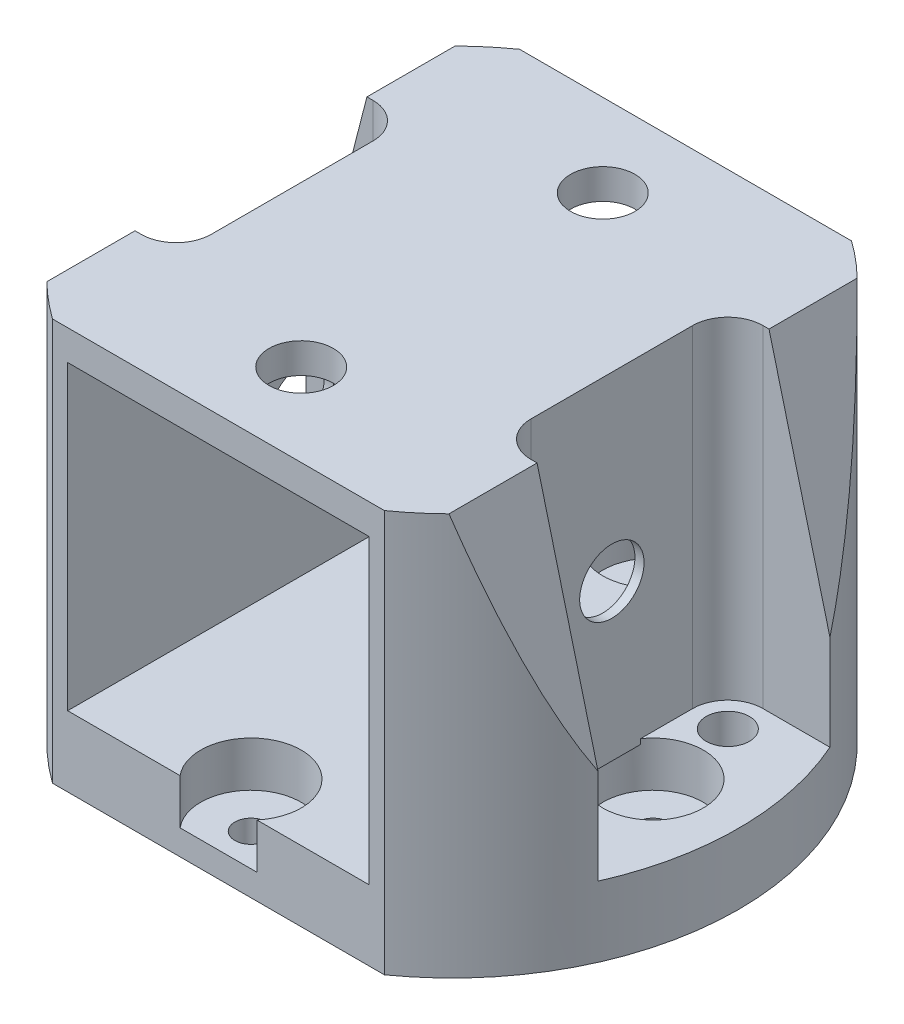
SolidWorks part; units mm, degrees
ref_plane "Front Plane" through (0, 0, 0) normal (0, 0, 1) x (1, 0, 0)
ref_plane "Top Plane" through (0, 0, 0) normal (0, 1, 0) x (1, 0, 0)
ref_plane "Right Plane" through (0, 0, 0) normal (1, 0, 0) x (0, 0, -1)
sketch "Sketch1" plane through (0, 0, 0) normal (0, 0, 1) x (1, 0, 0)
  line L0 (-28.5, 0) -> (-20, 33)
  line L1 (15, 0) -> (-15, 0)
  line L2 (15, 0) -> (15, 30)
  line L3 (15, 30) -> (-15, 30)
  line L4 (-15, 0) -> (-15, 30)
  line L5 (-20, 33) -> (20, 33)
  line L6 (20, 33) -> (28.5, 0)
  line L7 (28.5, 0) -> (28.5, -7)
  line L8 (28.5, -7) -> (-28.5, -7)
  line L9 (-28.5, -7) -> (-28.5, 0)
  line L10 (0, 0) -> (0, -7) construction
  point P15 (0, 33)
  point P16 (0, 30)
  dimension "D1" = 7
  dimension "D2" = 57
  dimension "D3" = 30
  dimension "D4" = 5
  dimension "D5" = 3
extrude "Boss-Extrude1" add sketch "Sketch1" along normal mid plane 57
sketch "Sketch3" plane through (0, 0, 0) normal (0, 1, 0) x (1, 0, 0)
  line L1 (-19.4015, 8.0364) -> (0, 0) construction
  line L2 (0, 0) -> (-20, 0) construction
  line L3 (20, -28.5) -> (-20, -28.5) construction
  line L4 (-15, 28.5) -> (15, 28.5) construction
  line L5 (-15, 28.5) -> (-15, -28.5) construction
  line L6 (-15, -28.5) -> (15, -28.5) construction
  line L7 (15, 28.5) -> (15, -28.5) construction
  line L8 (-15, 28.5) -> (15, -28.5) construction
  line L9 (-15, -28.5) -> (15, 28.5) construction
  circle A1 centre (-19.4015, 8.0364) radius 2.15
  circle A2 centre (-20, 0) radius 1.6
  circle A6 centre (-14.1421, 14.1421) radius 1.6
  circle A7 centre (-8.0364, 19.4015) radius 2.15
  circle A8 centre (0, 20) radius 1.6
  circle A9 centre (8.0364, 19.4015) radius 2.15
  circle A10 centre (14.1421, 14.1421) radius 1.6
  circle A11 centre (19.4015, 8.0364) radius 2.15
  circle A12 centre (20, 0) radius 1.6
  circle A13 centre (19.4015, -8.0364) radius 2.15
  circle A14 centre (14.1421, -14.1421) radius 1.6
  circle A15 centre (8.0364, -19.4015) radius 2.15
  circle A16 centre (0, -20) radius 1.6
  circle A17 centre (-8.0364, -19.4015) radius 2.15
  circle A18 centre (-14.1421, -14.1421) radius 1.6
  circle A19 centre (-19.4015, -8.0364) radius 2.15
  point P36 (0, 0)
  point P41 (0, 0)
  dimension "D2" = 4.3
  dimension "D3" = 3.2
  dimension "D1" = 22.5
  dimension "D4" = 21
  dimension "D5" = 20
  dimension "D7" = 30
  dimension "D6" = 8
extrude "Cut-Extrude1" cut sketch "Sketch3" against normal through all and the other way through all contours A13 | A12 | A1 | A2 | A19 | A11
sketch "Sketch4" plane through (0, 0, 0) normal (0, 1, 0) x (1, 0, 0)
  line L0 (0, 0) -> (16.5, 0) construction
  line L1 (0, 0) -> (0, 13.8087) construction
  line L8 (28.5, -28.5) -> (28.5, 28.5) construction
  line L9 (28.5, 11.5364) -> (19.4015, 11.5364)
  line L22 (28.5, 11.5364) -> (28.5, -11.5364)
  line L23 (28.5, -11.5364) -> (19.4015, -11.5364)
  line L24 (15.9015, 8.0364) -> (15.9015, 5)
  line L29 (15, -28.5) -> (15, 28.5) construction
  line L30 (15.9015, 5) -> (15, 5)
  line L32 (15.9015, -5) -> (15, -5)
  line L33 (15, 5) -> (15, -5)
  line L34 (15.9015, -5) -> (15.9015, -8.0364)
  line L36 (-15.9015, -5) -> (-15.9015, -8.0364)
  line L37 (-15, 5) -> (-15, -5)
  line L38 (-15.9015, -5) -> (-15, -5)
  line L39 (-15.9015, 5) -> (-15, 5)
  line L40 (-15.9015, 8.0364) -> (-15.9015, 5)
  line L41 (-28.5, -11.5364) -> (-19.4015, -11.5364)
  line L42 (-28.5, 11.5364) -> (-28.5, -11.5364)
  line L43 (-28.5, 11.5364) -> (-19.4015, 11.5364)
  circle A10 centre (19.4015, 8.0364) radius 3.5 construction
  circle A11 centre (20, 0) radius 4.5 construction
  circle A12 centre (19.4015, -8.0364) radius 3.5 construction
  arc A13 (19.4015, 11.5364) -> (15.9015, 8.0364) centre (19.4015, 8.0364) ccw
  arc A14 (19.4015, -11.5364) -> (15.9015, -8.0364) centre (19.4015, -8.0364) cw
  circle A17 centre (-19.4015, -8.0364) radius 3.5 construction
  circle A18 centre (-20, 0) radius 4.5 construction
  circle A19 centre (-19.4015, 8.0364) radius 3.5 construction
  arc A20 (-19.4015, -11.5364) -> (-15.9015, -8.0364) centre (-19.4015, -8.0364) ccw
  arc A21 (-19.4015, 11.5364) -> (-15.9015, 8.0364) centre (-19.4015, 8.0364) cw
  point P36 (15, -2.4042)
  point P39 (15, 0)
  point P40 (1.8992, 6.3615)
  dimension "D1" = 7
  dimension "D2" = 9
  dimension "D3" = 10
extrude "Cut-Extrude2" cut sketch "Sketch4" along normal through all
sketch "Sketch5" plane through (0, 0, 0) normal (0, 1, 0) x (1, 0, 0)
  line L0 (20, 28.5) -> (-20, 28.5) construction
  circle A0 centre (0, 0) radius 28.5
extrude "Cut-Extrude3" cut sketch "Sketch5" against normal through all both and the other way through all flip side to cut
sketch "Sketch6" plane through (0, 0, 0) normal (0, 1, 0) x (1, 0, 0)
  line L0 (-16.5066, -23.2332) -> (16.5066, -23.2332)
  line L2 (-16.5066, 23.2332) -> (16.5066, 23.2332)
  line L3 (-15, -24.2332) -> (15, -24.2332) construction
  line L4 (0, 0) -> (-9.0699, 0) construction
  arc A0 (-16.5066, 23.2332) -> (16.5066, 23.2332) centre (0, 0) cw
  arc A2 (-20, -20.3039) -> (20, -20.3039) centre (0, 0) ccw construction
  arc A3 (-16.5066, -23.2332) -> (16.5066, -23.2332) centre (0, 0) ccw
  dimension "D1" = 1
extrude "Cut-Extrude4" cut sketch "Sketch6" along normal through all both and the other way through all
sketch "Sketch7" plane through (0, -7, 0) normal (0, -1, 0) x (1, 0, 0)
  line L0 (0, 0) -> (-10.7418, -4.4494) construction
  line L1 (-15, 28.5) -> (15, -28.5) construction
  line L2 (-19.4015, -8.0364) -> (0, 0) construction
  circle A3 centre (0, 20) radius 5 construction
  circle A4 centre (-14.1421, 14.1421) radius 5
  circle A5 centre (0, -20) radius 5 construction
  circle A6 centre (14.1421, -14.1421) radius 5
  circle A7 centre (-14.1421, -14.1421) radius 5
  circle A8 centre (14.1421, 14.1421) radius 5
  dimension "D1" = 10
extrude "Cut-Extrude5" cut sketch "Sketch7" against normal blind 4.5
extrude "Cut-Extrude6" cut sketch "Sketch3<3>" against normal through all contours A16 | A8
sketch "Sketch3<3>" plane through (0, 0, 0) normal (0, 1, 0) x (1, 0, 0) same geometry as "Sketch3"
sketch "Sketch8" plane through (0, 0, 0) normal (0, 1, 0) x (1, 0, 0)
  circle A0 centre (0, -20) radius 5
  circle A1 centre (0, 20) radius 5
  circle A2 centre (-20, 0) radius 5
  circle A3 centre (20, 0) radius 5
  dimension "D1" = 10
extrude "Cut-Extrude7" cut sketch "Sketch8" against normal blind 4.5
sketch "Sketch9" plane through (0, 33, 0) normal (0, 1, 0) x (1, 0, 0)
  line L1 (-15, 5) -> (-15.9015, 5)
  line L2 (-15, 5) -> (-15, -5)
  line L3 (-15, -5) -> (-15.9015, -5)
  line L4 (-15.9015, 5) -> (-15.9015, -5)
  line L5 (15, 5) -> (15.9015, 5)
  line L6 (15, 5) -> (15, -5)
  line L7 (15, -5) -> (15.9015, -5)
  line L8 (15.9015, 5) -> (15.9015, -5)
  point P11 (15.9015, -5)
extrude "Boss-Extrude2" add sketch "Sketch9" against normal offset from surface (33.5 mm away) 0.5 up to face at (0, 0, 0) offset beyond the face yes
sketch "Sketch10" plane through (0, 0, 0) normal (1, 0, 0) x (0, 0, -1)
  line L0 (0, 15) -> (0, 0) construction
  circle A0 centre (0, 15) radius 3.2
  dimension "D2" = 6.4
  dimension "D1" = 15
extrude "Cut-Extrude9" cut sketch "Sketch10" against normal through all both and the other way through all
sketch "Sketch11" plane through (0, 33, 0) normal (0, 1, 0) x (1, 0, 0)
  line L0 (0, -15) -> (0, 15) construction
  circle A0 centre (0, 15) radius 3.2
  circle A1 centre (0, -15) radius 3.2
  point P4 (0, 0)
  dimension "D1" = 6.4
  dimension "D2" = 30
extrude "Cut-Extrude10" cut sketch "Sketch11" against normal up to next and the other way through all
